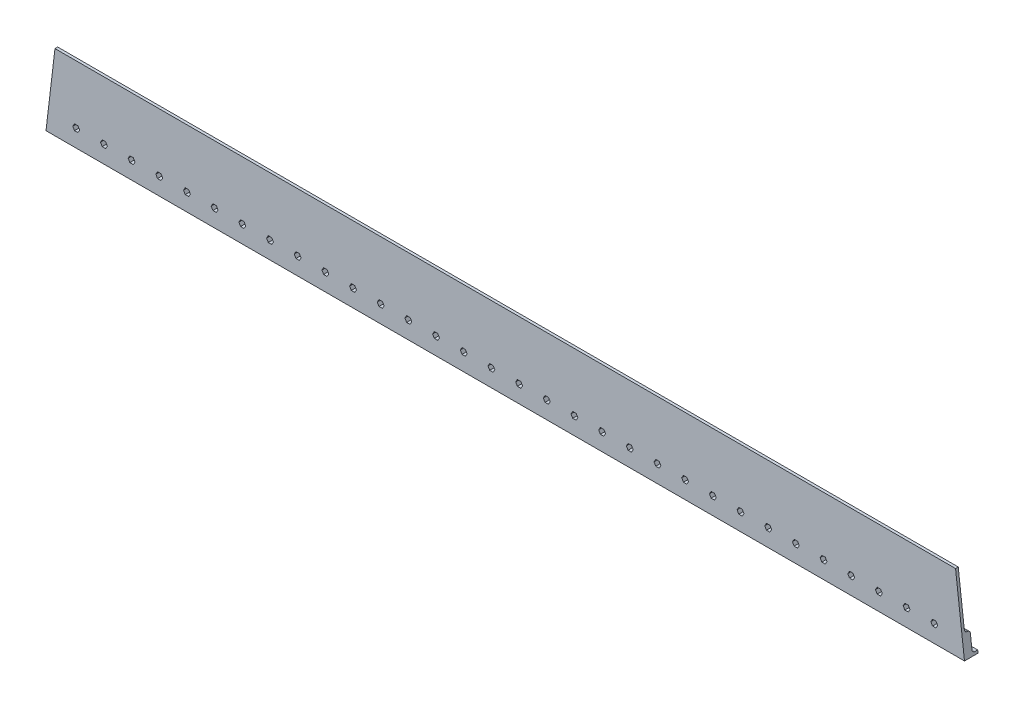
SolidWorks part; units mm, degrees
material "AISI 4340 Steel, annealed"
ref_plane "Front Plane" through (0, 0, 0) normal (0, 0, 1) x (1, 0, 0)
ref_plane "Top Plane" through (0, 0, 0) normal (0, 1, 0) x (1, 0, 0)
ref_plane "Right Plane" through (0, 0, 0) normal (1, 0, 0) x (0, 0, -1)
sketch "Sketch1" plane through (0, 0, 0) normal (1, 0, 0) x (0, 0, -1)
  line L0 (0, 0) -> (0, 140)
  line L1 (0, 140) -> (5, 140)
  line L2 (5, 140) -> (5, 40)
  line L3 (5, 40) -> (15, 40)
  line L4 (15, 40) -> (15, 5)
  line L5 (15, 5) -> (25, 5)
  line L6 (25, 5) -> (25, 0)
  line L7 (25, 0) -> (0, 0)
  dimension "D1" = 5
  dimension "D2" = 10
  dimension "D3" = 25
  dimension "D4" = 5
  dimension "D5" = 40
  dimension "D6" = 140
extrude "General extrude" add sketch "Sketch1" along normal mid plane 1700.14
fillet "Rounding" radius 5 3 edges at (0, 5, -15) (0, 40, -15) (0, 40, -5)
sketch "Sketch2" plane through (0, 0, 0) normal (0, 0, 1) x (1, 0, 0)
  line L0 (-850.07, 0) -> (-850.07, 140)
  line L1 (-850.07, 140) -> (-833.4909, 140)
  line L2 (850.07, 140) -> (-850.07, 140) construction
  line L3 (-833.4909, 140) -> (-850.07, 0)
  line L4 (0, -13.75) -> (0, 13.75) construction
  line L5 (833.4909, 140) -> (850.07, 0)
  line L6 (850.07, 140) -> (833.4909, 140)
  line L7 (850.07, 0) -> (850.07, 140)
  dimension "D1" = 6.754
extrude "Slant cut (to fit with horizonal siding)" cut sketch "Sketch2" against normal through all both and the other way through all
sketch "Sketch3" plane through (0, 0, 0) normal (0, 0, 1) x (1, 0, 0)
  line L0 (850.07, 0) -> (-850.07, 0) construction
  line L4 (-790.9253, 26.5) -> (-787.7498, 32)
  line L5 (-787.7498, 32) -> (-790.9253, 37.5)
  line L6 (-790.9253, 37.5) -> (-797.2761, 37.5)
  line L7 (-797.2761, 37.5) -> (-800.4515, 32)
  line L8 (-800.4515, 32) -> (-797.2761, 26.5)
  line L9 (-797.2761, 26.5) -> (-790.9253, 26.5)
  line L10 (-845.3331, 40) -> (845.3331, 40) construction
  line L11 (-833.4909, 140) -> (-850.07, 0) construction
  line L12 (850.07, 0) -> (833.4909, 140) construction
  line L13 (-739.693, 26.5) -> (-736.5175, 32)
  line L14 (-736.5175, 32) -> (-739.693, 37.5)
  line L15 (-739.693, 37.5) -> (-746.0438, 37.5)
  line L16 (-746.0438, 37.5) -> (-749.2192, 32)
  line L17 (-749.2192, 32) -> (-746.0438, 26.5)
  line L18 (-746.0438, 26.5) -> (-739.693, 26.5)
  line L19 (-688.4607, 26.5) -> (-685.2852, 32)
  line L20 (-685.2852, 32) -> (-688.4607, 37.5)
  line L21 (-688.4607, 37.5) -> (-694.8115, 37.5)
  line L22 (-694.8115, 37.5) -> (-697.9869, 32)
  line L23 (-697.9869, 32) -> (-694.8115, 26.5)
  line L24 (-694.8115, 26.5) -> (-688.4607, 26.5)
  line L25 (-637.2284, 26.5) -> (-634.0529, 32)
  line L26 (-634.0529, 32) -> (-637.2284, 37.5)
  line L27 (-637.2284, 37.5) -> (-643.5792, 37.5)
  line L28 (-643.5792, 37.5) -> (-646.7546, 32)
  line L29 (-646.7546, 32) -> (-643.5792, 26.5)
  line L30 (-643.5792, 26.5) -> (-637.2284, 26.5)
  line L31 (-585.9961, 26.5) -> (-582.8206, 32)
  line L32 (-582.8206, 32) -> (-585.9961, 37.5)
  line L33 (-585.9961, 37.5) -> (-592.3469, 37.5)
  line L34 (-592.3469, 37.5) -> (-595.5223, 32)
  line L35 (-595.5223, 32) -> (-592.3469, 26.5)
  line L36 (-592.3469, 26.5) -> (-585.9961, 26.5)
  line L37 (-534.7637, 26.5) -> (-531.5883, 32)
  line L38 (-531.5883, 32) -> (-534.7637, 37.5)
  line L39 (-534.7637, 37.5) -> (-541.1146, 37.5)
  line L40 (-541.1146, 37.5) -> (-544.29, 32)
  line L41 (-544.29, 32) -> (-541.1146, 26.5)
  line L42 (-541.1146, 26.5) -> (-534.7637, 26.5)
  line L43 (-483.5314, 26.5) -> (-480.356, 32)
  line L44 (-480.356, 32) -> (-483.5314, 37.5)
  line L45 (-483.5314, 37.5) -> (-489.8823, 37.5)
  line L46 (-489.8823, 37.5) -> (-493.0577, 32)
  line L47 (-493.0577, 32) -> (-489.8823, 26.5)
  line L48 (-489.8823, 26.5) -> (-483.5314, 26.5)
  line L49 (-432.2991, 26.5) -> (-429.1237, 32)
  line L50 (-429.1237, 32) -> (-432.2991, 37.5)
  line L51 (-432.2991, 37.5) -> (-438.65, 37.5)
  line L52 (-438.65, 37.5) -> (-441.8254, 32)
  line L53 (-441.8254, 32) -> (-438.65, 26.5)
  line L54 (-438.65, 26.5) -> (-432.2991, 26.5)
  line L55 (-381.0668, 26.5) -> (-377.8914, 32)
  line L56 (-377.8914, 32) -> (-381.0668, 37.5)
  line L57 (-381.0668, 37.5) -> (-387.4177, 37.5)
  line L58 (-387.4177, 37.5) -> (-390.5931, 32)
  line L59 (-390.5931, 32) -> (-387.4177, 26.5)
  line L60 (-387.4177, 26.5) -> (-381.0668, 26.5)
  line L61 (-329.8345, 26.5) -> (-326.6591, 32)
  line L62 (-326.6591, 32) -> (-329.8345, 37.5)
  line L63 (-329.8345, 37.5) -> (-336.1854, 37.5)
  line L64 (-336.1854, 37.5) -> (-339.3608, 32)
  line L65 (-339.3608, 32) -> (-336.1854, 26.5)
  line L66 (-336.1854, 26.5) -> (-329.8345, 26.5)
  line L67 (-278.6022, 26.5) -> (-275.4268, 32)
  line L68 (-275.4268, 32) -> (-278.6022, 37.5)
  line L69 (-278.6022, 37.5) -> (-284.9531, 37.5)
  line L70 (-284.9531, 37.5) -> (-288.1285, 32)
  line L71 (-288.1285, 32) -> (-284.9531, 26.5)
  line L72 (-284.9531, 26.5) -> (-278.6022, 26.5)
  line L73 (-227.3699, 26.5) -> (-224.1945, 32)
  line L74 (-224.1945, 32) -> (-227.3699, 37.5)
  line L75 (-227.3699, 37.5) -> (-233.7208, 37.5)
  line L76 (-233.7208, 37.5) -> (-236.8962, 32)
  line L77 (-236.8962, 32) -> (-233.7208, 26.5)
  line L78 (-233.7208, 26.5) -> (-227.3699, 26.5)
  line L79 (-176.1376, 26.5) -> (-172.9622, 32)
  line L80 (-172.9622, 32) -> (-176.1376, 37.5)
  line L81 (-176.1376, 37.5) -> (-182.4885, 37.5)
  line L82 (-182.4885, 37.5) -> (-185.6639, 32)
  line L83 (-185.6639, 32) -> (-182.4885, 26.5)
  line L84 (-182.4885, 26.5) -> (-176.1376, 26.5)
  line L85 (-124.9053, 26.5) -> (-121.7299, 32)
  line L86 (-121.7299, 32) -> (-124.9053, 37.5)
  line L87 (-124.9053, 37.5) -> (-131.2562, 37.5)
  line L88 (-131.2562, 37.5) -> (-134.4316, 32)
  line L89 (-134.4316, 32) -> (-131.2562, 26.5)
  line L90 (-131.2562, 26.5) -> (-124.9053, 26.5)
  line L91 (-73.673, 26.5) -> (-70.4976, 32)
  line L92 (-70.4976, 32) -> (-73.673, 37.5)
  line L93 (-73.673, 37.5) -> (-80.0239, 37.5)
  line L94 (-80.0239, 37.5) -> (-83.1993, 32)
  line L95 (-83.1993, 32) -> (-80.0239, 26.5)
  line L96 (-80.0239, 26.5) -> (-73.673, 26.5)
  line L97 (-22.4407, 26.5) -> (-19.2653, 32)
  line L98 (-19.2653, 32) -> (-22.4407, 37.5)
  line L99 (-22.4407, 37.5) -> (-28.7916, 37.5)
  line L100 (-28.7916, 37.5) -> (-31.967, 32)
  line L101 (-31.967, 32) -> (-28.7916, 26.5)
  line L102 (-28.7916, 26.5) -> (-22.4407, 26.5)
  line L103 (28.7916, 26.5) -> (31.967, 32)
  line L104 (31.967, 32) -> (28.7916, 37.5)
  line L105 (28.7916, 37.5) -> (22.4407, 37.5)
  line L106 (22.4407, 37.5) -> (19.2653, 32)
  line L107 (19.2653, 32) -> (22.4407, 26.5)
  line L108 (22.4407, 26.5) -> (28.7916, 26.5)
  line L109 (80.0239, 26.5) -> (83.1993, 32)
  line L110 (83.1993, 32) -> (80.0239, 37.5)
  line L111 (80.0239, 37.5) -> (73.673, 37.5)
  line L112 (73.673, 37.5) -> (70.4976, 32)
  line L113 (70.4976, 32) -> (73.673, 26.5)
  line L114 (73.673, 26.5) -> (80.0239, 26.5)
  line L115 (131.2562, 26.5) -> (134.4316, 32)
  line L116 (134.4316, 32) -> (131.2562, 37.5)
  line L117 (131.2562, 37.5) -> (124.9053, 37.5)
  line L118 (124.9053, 37.5) -> (121.7299, 32)
  line L119 (121.7299, 32) -> (124.9053, 26.5)
  line L120 (124.9053, 26.5) -> (131.2562, 26.5)
  line L121 (182.4885, 26.5) -> (185.6639, 32)
  line L122 (185.6639, 32) -> (182.4885, 37.5)
  line L123 (182.4885, 37.5) -> (176.1376, 37.5)
  line L124 (176.1376, 37.5) -> (172.9622, 32)
  line L125 (172.9622, 32) -> (176.1376, 26.5)
  line L126 (176.1376, 26.5) -> (182.4885, 26.5)
  line L127 (233.7208, 26.5) -> (236.8962, 32)
  line L128 (236.8962, 32) -> (233.7208, 37.5)
  line L129 (233.7208, 37.5) -> (227.3699, 37.5)
  line L130 (227.3699, 37.5) -> (224.1945, 32)
  line L131 (224.1945, 32) -> (227.3699, 26.5)
  line L132 (227.3699, 26.5) -> (233.7208, 26.5)
  line L133 (284.9531, 26.5) -> (288.1285, 32)
  line L134 (288.1285, 32) -> (284.9531, 37.5)
  line L135 (284.9531, 37.5) -> (278.6022, 37.5)
  line L136 (278.6022, 37.5) -> (275.4268, 32)
  line L137 (275.4268, 32) -> (278.6022, 26.5)
  line L138 (278.6022, 26.5) -> (284.9531, 26.5)
  line L139 (336.1854, 26.5) -> (339.3608, 32)
  line L140 (339.3608, 32) -> (336.1854, 37.5)
  line L141 (336.1854, 37.5) -> (329.8345, 37.5)
  line L142 (329.8345, 37.5) -> (326.6591, 32)
  line L143 (326.6591, 32) -> (329.8345, 26.5)
  line L144 (329.8345, 26.5) -> (336.1854, 26.5)
  line L145 (387.4177, 26.5) -> (390.5931, 32)
  line L146 (390.5931, 32) -> (387.4177, 37.5)
  line L147 (387.4177, 37.5) -> (381.0668, 37.5)
  line L148 (381.0668, 37.5) -> (377.8914, 32)
  line L149 (377.8914, 32) -> (381.0668, 26.5)
  line L150 (381.0668, 26.5) -> (387.4177, 26.5)
  line L151 (438.65, 26.5) -> (441.8254, 32)
  line L152 (441.8254, 32) -> (438.65, 37.5)
  line L153 (438.65, 37.5) -> (432.2991, 37.5)
  line L154 (432.2991, 37.5) -> (429.1237, 32)
  line L155 (429.1237, 32) -> (432.2991, 26.5)
  line L156 (432.2991, 26.5) -> (438.65, 26.5)
  line L157 (489.8823, 26.5) -> (493.0577, 32)
  line L158 (493.0577, 32) -> (489.8823, 37.5)
  line L159 (489.8823, 37.5) -> (483.5314, 37.5)
  line L160 (483.5314, 37.5) -> (480.356, 32)
  line L161 (480.356, 32) -> (483.5314, 26.5)
  line L162 (483.5314, 26.5) -> (489.8823, 26.5)
  line L163 (541.1146, 26.5) -> (544.29, 32)
  line L164 (544.29, 32) -> (541.1146, 37.5)
  line L165 (541.1146, 37.5) -> (534.7637, 37.5)
  line L166 (534.7637, 37.5) -> (531.5883, 32)
  line L167 (531.5883, 32) -> (534.7637, 26.5)
  line L168 (534.7637, 26.5) -> (541.1146, 26.5)
  line L169 (592.3469, 26.5) -> (595.5223, 32)
  line L170 (595.5223, 32) -> (592.3469, 37.5)
  line L171 (592.3469, 37.5) -> (585.9961, 37.5)
  line L172 (585.9961, 37.5) -> (582.8206, 32)
  line L173 (582.8206, 32) -> (585.9961, 26.5)
  line L174 (585.9961, 26.5) -> (592.3469, 26.5)
  line L175 (643.5792, 26.5) -> (646.7546, 32)
  line L176 (646.7546, 32) -> (643.5792, 37.5)
  line L177 (643.5792, 37.5) -> (637.2284, 37.5)
  line L178 (637.2284, 37.5) -> (634.0529, 32)
  line L179 (634.0529, 32) -> (637.2284, 26.5)
  line L180 (637.2284, 26.5) -> (643.5792, 26.5)
  line L181 (694.8115, 26.5) -> (697.9869, 32)
  line L182 (697.9869, 32) -> (694.8115, 37.5)
  line L183 (694.8115, 37.5) -> (688.4607, 37.5)
  line L184 (688.4607, 37.5) -> (685.2852, 32)
  line L185 (685.2852, 32) -> (688.4607, 26.5)
  line L186 (688.4607, 26.5) -> (694.8115, 26.5)
  line L187 (746.0438, 26.5) -> (749.2192, 32)
  line L188 (749.2192, 32) -> (746.0438, 37.5)
  line L189 (746.0438, 37.5) -> (739.693, 37.5)
  line L190 (739.693, 37.5) -> (736.5175, 32)
  line L191 (736.5175, 32) -> (739.693, 26.5)
  line L192 (739.693, 26.5) -> (746.0438, 26.5)
  line L193 (797.2761, 26.5) -> (800.4515, 32)
  line L194 (800.4515, 32) -> (797.2761, 37.5)
  line L195 (797.2761, 37.5) -> (790.9253, 37.5)
  line L196 (790.9253, 37.5) -> (787.7498, 32)
  line L197 (787.7498, 32) -> (790.9253, 26.5)
  line L198 (790.9253, 26.5) -> (797.2761, 26.5)
  circle A0 centre (-794.1007, 32) radius 5.5 construction
  circle A1 centre (794.1007, 32) radius 5.5 construction
  point P204 (0, 0)
  point P205 (794.1007, 37.5)
  point P206 (0, 0)
  dimension "D1" = 11
  dimension "D2" = 40
  dimension "D3" = 5
  dimension "D4" = 51.2324
  dimension "D6" = 51.2324
  dimension "D5" = 32
extrude "Roller cuts" cut sketch "Sketch3" against normal through all both and the other way through all
